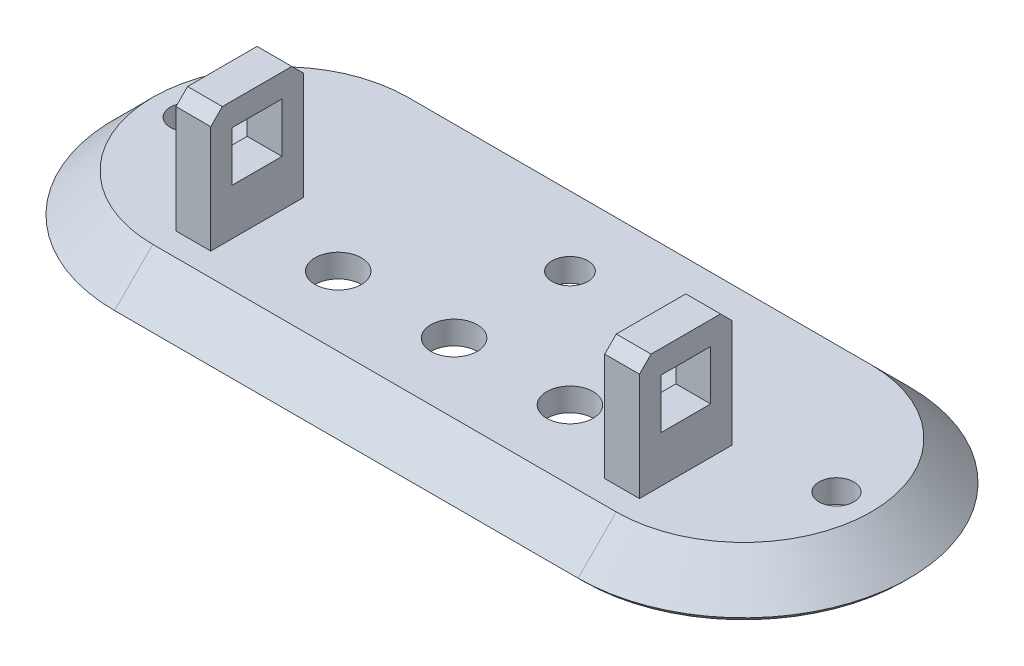
SolidWorks part; units mm, degrees
ref_plane "Plan de face" through (0, 0, 0) normal (0, 0, 1) x (1, 0, 0)
ref_plane "Plan de dessus" through (0, 0, 0) normal (0, 1, 0) x (1, 0, 0)
ref_plane "Plan de droite" through (0, 0, 0) normal (1, 0, 0) x (0, 0, -1)
sketch "Esquisse1" plane through (0, 0, 0) normal (0, 1, 0) x (1, 0, 0)
  line L0 (-20, 0) -> (20, 0) construction
  line L1 (-20, 14.8) -> (20, 14.8)
  line L2 (-20, -14.8) -> (20, -14.8)
  arc A0 (-20, 14.8) -> (-20, -14.8) centre (-20, 0) ccw
  arc A1 (20, -14.8) -> (20, 14.8) centre (20, 0) ccw
  point P3 (0, 0)
  dimension "D1" = 14.8
  dimension "D2" = 40
extrude "Boss.-Extru.1" add sketch "Esquisse1" along normal blind 3.8 draft 45
shell "Coque2" thickness 2 removed face at (0, 0, 0)
chamfer "Chanfrein1" distance 1 angle 45 4 edges at (-34.8, 0, 0) (0, 0, 14.8) (0, 0, -14.8) (34.8, 0, 0) first distance on face at (0, 0, 0)
sketch "Esquisse2" plane through (0, 3.8, 0) normal (0, 1, 0) x (1, 0, 0)
  line L0 (0, 11) -> (0, -11) construction
  line L1 (20, 11) -> (-20, 11) construction
  line L2 (-20, -11) -> (20, -11) construction
  circle A0 centre (-28, 0) radius 1.5
  circle A1 centre (28, 0) radius 1.5
  point P2 (0, 0)
  dimension "D1" = 3
  dimension "D2" = 8
extrude "Enlèv. mat.-Extru.1" cut sketch "Esquisse2" against normal up to next
sketch "Esquisse3" plane through (0, 1.8, 0) normal (0, -1, 0) x (1, 0, 0)
  line L0 (0, 0) -> (18.2371, 0) construction
  circle A0 centre (0, -5) radius 1.55
  circle A1 centre (10, 5) radius 2
  circle A2 centre (0, 5) radius 2
  circle A3 centre (-10, 5) radius 2
  dimension "D1" = 3.1
  dimension "D2" = 4
  dimension "D3" = 5
  dimension "D4" = 5
  dimension "D5" = 10
  dimension "D6" = 3
extrude "Enlèv. mat.-Extru.2" cut sketch "Esquisse3" against normal up to next
ref_plane "Plan1" through (20, 0, 0) normal (-1, 0, 0) x (0, 0, 1)
sketch "Esquisse4" plane through (20, 0, 0) normal (-1, 0, 0) x (0, 0, 1)
  line L0 (7, 3.8) -> (3, 3.8) construction
  line L1 (9, 3.8) -> (1, 3.8)
  line L2 (9, 3.8) -> (9, 14.1)
  line L3 (9, 14.1) -> (5, 14.1)
  line L4 (5, 3.8) -> (5, 7.8) construction
  line L5 (1, 3.8) -> (1, 14.1)
  line L6 (7.15, 7.8) -> (2.85, 7.8)
  line L7 (7.15, 7.8) -> (7.15, 12.1)
  line L8 (7.15, 12.1) -> (2.85, 12.1)
  line L9 (2.85, 7.8) -> (2.85, 12.1)
  line L11 (1, 14.1) -> (5, 14.1)
  point P15 (0, 0)
  dimension "D1" = 0
  dimension "D2" = 4
  dimension "D3" = 2
  dimension "D4" = 2.15
  dimension "D6" = 4.3
  dimension "D7" = 4
  dimension "D8" = 5
extrude "Boss.-Extru.2" add sketch "Esquisse4" along normal blind 3
chamfer "Chanfrein2" distance 1 angle 45 2 edges at (18.5, 14.1, 1) (18.5, 14.1, 9)
ref_plane "Plan2" through (-20, 0, 0) normal (1, 0, 0) x (0, 0, -1)
ref_plane "Plan3" through (0, 0, 0) normal (1, 0, 0) x (0, 0, -1)
mirror "Symétrie1" about plane through (0, 0, 0) normal (1, 0, 0) of "Chanfrein2", "Boss.-Extru.2"
